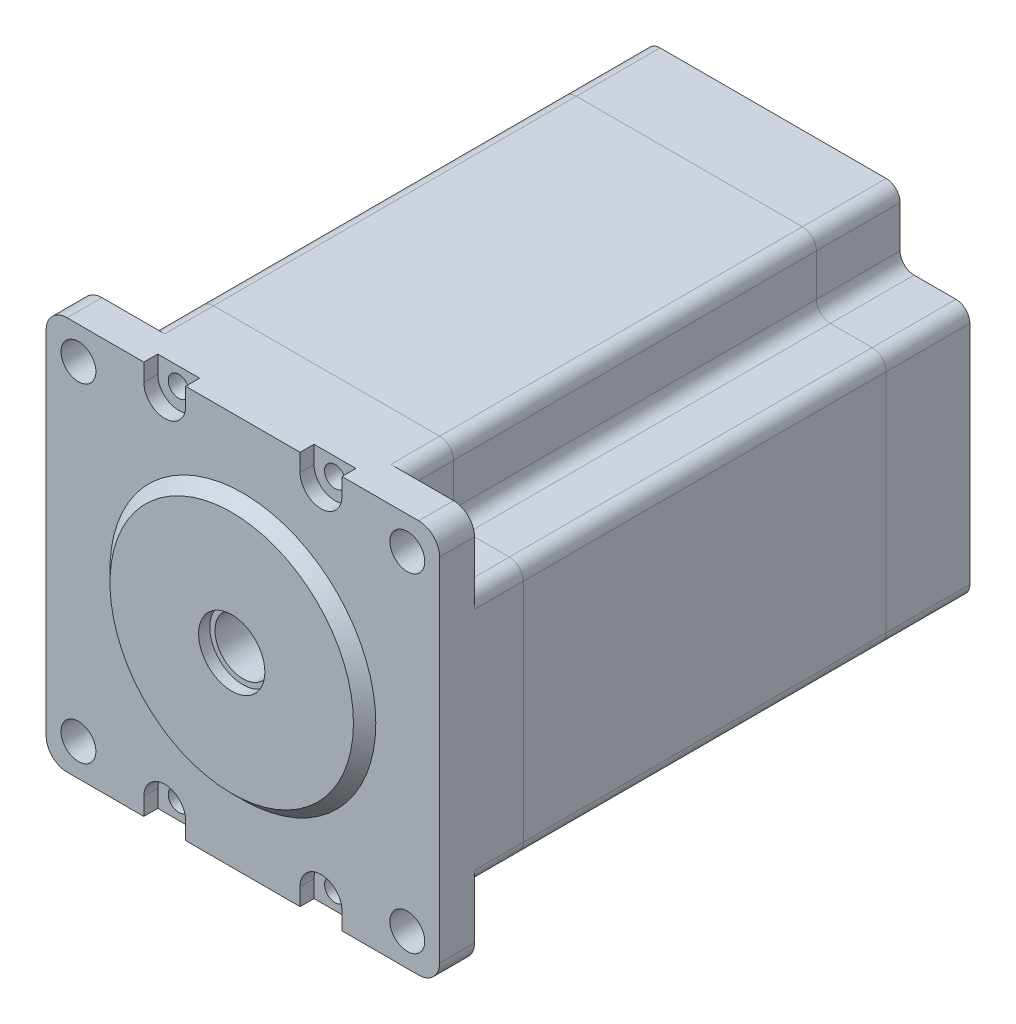
SolidWorks part; units mm, degrees
ref_plane "Ön Düzlem" through (0, 0, 0) normal (0, 0, 1) x (1, 0, 0)
ref_plane "Üst Düzlem" through (0, 0, 0) normal (0, 1, 0) x (1, 0, 0)
ref_plane "Sağ Düzlem" through (0, 0, 0) normal (1, 0, 0) x (0, 0, -1)
sketch "Çizim2" plane through (0, 0, 0) normal (0, 0, 1) x (1, 0, 0)
  line L0 (-28.2, 0) -> (28.2, 0) construction
  line L1 (-25.2, 28.2) -> (25.2, 28.2)
  line L2 (-28.2, 25.2) -> (-28.2, -25.2)
  line L3 (-25.2, -28.2) -> (25.2, -28.2)
  line L4 (28.2, 25.2) -> (28.2, -25.2)
  line L5 (-28.2, 28.2) -> (28.2, -28.2) construction
  line L6 (-28.2, -28.2) -> (28.2, 28.2) construction
  arc A0 (-28.2, -25.2) -> (-25.2, -28.2) centre (-25.2, -25.2) ccw
  arc A1 (25.2, -28.2) -> (28.2, -25.2) centre (25.2, -25.2) ccw
  arc A2 (25.2, 28.2) -> (28.2, 25.2) centre (25.2, 25.2) cw
  arc A3 (-25.2, 28.2) -> (-28.2, 25.2) centre (-25.2, 25.2) ccw
  circle A4 centre (-23.57, 23.57) radius 2.5
  circle A5 centre (23.57, 23.57) radius 2.5
  circle A6 centre (23.57, -23.57) radius 2.5
  circle A7 centre (-23.57, -23.57) radius 2.5
  point P0 (0, 0)
  dimension "D3" = 3
  dimension "D5" = 5
  dimension "D6" = 5
  dimension "D1" = 56.4
  dimension "D2" = 56.4
  dimension "D4" = 47.14
extrude "Yükseklik-Ekstrüzyon1" add sketch "Çizim2" along normal blind 5
sketch "Çizim4" plane through (0, 0, 0) normal (0, 0, -1) x (-1, 0, 0)
  line L0 (-18.2, 26.2) -> (-18.2, 20.2)
  line L1 (-25.2, 28.2) -> (25.2, 28.2) construction
  line L2 (-20.2, 18.2) -> (-26.2, 18.2)
  line L3 (-28.2, -25.2) -> (-28.2, 25.2) construction
  line L4 (26.2, 18.2) -> (20.2, 18.2)
  line L5 (18.2, 20.2) -> (18.2, 26.2)
  line L6 (18.2, -26.2) -> (18.2, -20.2)
  line L7 (20.2, -18.2) -> (26.2, -18.2)
  line L8 (-26.2, -18.2) -> (-20.2, -18.2)
  line L9 (-18.2, -20.2) -> (-18.2, -26.2)
  line L10 (-16.2, 28.2) -> (16.2, 28.2)
  line L11 (28.2, 16.2) -> (28.2, -16.2)
  line L12 (16.2, -28.2) -> (-16.2, -28.2)
  line L13 (-28.2, -16.2) -> (-28.2, 16.2)
  arc A0 (-26.2, -18.2) -> (-28.2, -16.2) centre (-26.2, -16.2) cw
  arc A1 (-20.2, -18.2) -> (-18.2, -20.2) centre (-20.2, -20.2) cw
  arc A2 (-18.2, -26.2) -> (-16.2, -28.2) centre (-16.2, -26.2) ccw
  arc A3 (18.2, -26.2) -> (16.2, -28.2) centre (16.2, -26.2) cw
  arc A4 (18.2, -20.2) -> (20.2, -18.2) centre (20.2, -20.2) cw
  arc A5 (26.2, -18.2) -> (28.2, -16.2) centre (26.2, -16.2) ccw
  arc A6 (26.2, 18.2) -> (28.2, 16.2) centre (26.2, 16.2) cw
  arc A7 (20.2, 18.2) -> (18.2, 20.2) centre (20.2, 20.2) cw
  arc A8 (18.2, 26.2) -> (16.2, 28.2) centre (16.2, 26.2) ccw
  arc A9 (-26.2, 18.2) -> (-28.2, 16.2) centre (-26.2, 16.2) ccw
  arc A10 (-18.2, 26.2) -> (-16.2, 28.2) centre (-16.2, 26.2) cw
  arc A11 (-18.2, 20.2) -> (-20.2, 18.2) centre (-20.2, 20.2) cw
  point P19 (0, 0)
  point P37 (-28.2, 18.2)
  point P40 (-18.2, 28.2)
  dimension "D4" = 2
  dimension "D1" = 10
  dimension "D2" = 10
  dimension "D3" = 4
extrude "Yükseklik-Ekstrüzyon2" add sketch "Çizim4" along normal blind 7
sketch "Çizim5" plane through (0, 0, 5) normal (0, 0, 1) x (1, 0, 0)
  line L0 (-14.2, 28.2) -> (-14.2, 25.7)
  line L1 (25.2, 28.2) -> (-25.2, 28.2) construction
  line L2 (-8.2, 28.2) -> (-8.2, 25.7)
  line L3 (-28.2, 25.2) -> (-28.2, -25.2) construction
  line L4 (-14.2, 28.2) -> (-8.2, 28.2)
  line L5 (-28.2, 0) -> (28.2, 0) construction
  line L6 (28.2, -25.2) -> (28.2, 25.2) construction
  line L7 (0, 28.2) -> (0, -28.2) construction
  line L8 (-25.2, -28.2) -> (25.2, -28.2) construction
  line L9 (-14.2, -28.2) -> (-8.2, -28.2)
  line L10 (-8.2, -28.2) -> (-8.2, -25.7)
  line L11 (-14.2, -28.2) -> (-14.2, -25.7)
  line L12 (14.2, -28.2) -> (14.2, -25.7)
  line L13 (8.2, -28.2) -> (8.2, -25.7)
  line L14 (14.2, -28.2) -> (8.2, -28.2)
  line L15 (14.2, 28.2) -> (8.2, 28.2)
  line L16 (8.2, 28.2) -> (8.2, 25.7)
  line L17 (14.2, 28.2) -> (14.2, 25.7)
  arc A0 (-14.2, 25.7) -> (-8.2, 25.7) centre (-11.2, 25.7) ccw
  arc A1 (-14.2, -25.7) -> (-8.2, -25.7) centre (-11.2, -25.7) cw
  arc A2 (14.2, -25.7) -> (8.2, -25.7) centre (11.2, -25.7) ccw
  arc A3 (14.2, 25.7) -> (8.2, 25.7) centre (11.2, 25.7) cw
  dimension "D1" = 14
  dimension "D2" = 6
  dimension "D3" = 2.5
  dimension "D4" = 2.5
extrude "Kes-Ekstrüzyon1" cut sketch "Çizim5" against normal blind 2
sketch "Çizim6" plane through (0, 0, 5) normal (0, 0, 1) x (1, 0, 0)
  circle A0 centre (0, 0) radius 19.05
  dimension "D1" = 38.1
extrude "Yükseklik-Ekstrüzyon3" add sketch "Çizim6" along normal blind 1.6 separate body
chamfer "Pah1" distance 1.6 angle 45 1 edges at (19.05, 0, 6.6)
sketch "Çizim7" plane through (0, 0, 6.6) normal (0, 0, 1) x (1, 0, 0)
  circle A0 centre (0, 0) radius 4
  dimension "D1" = 8
sketch "Çizim8" plane through (0, 0, -7) normal (0, 0, -1) x (-1, 0, 0)
  line L12 (-26.2, -18.2) -> (-20.2, -18.2)
  line L13 (-18.2, -20.2) -> (-18.2, -26.2)
  line L14 (-16.2, -28.2) -> (16.2, -28.2)
  line L15 (18.2, -26.2) -> (18.2, -20.2)
  line L16 (20.2, -18.2) -> (26.2, -18.2)
  line L17 (28.2, -16.2) -> (28.2, 16.2)
  line L18 (26.2, 18.2) -> (20.2, 18.2)
  line L19 (18.2, 20.2) -> (18.2, 26.2)
  line L20 (16.2, 28.2) -> (-16.2, 28.2)
  line L21 (-18.2, 26.2) -> (-18.2, 20.2)
  line L22 (-20.2, 18.2) -> (-26.2, 18.2)
  line L23 (-28.2, 16.2) -> (-28.2, -16.2)
  line L24 (-26.2, -18.2) -> (-20.2, -18.2)
  line L25 (-18.2, -20.2) -> (-18.2, -26.2)
  line L26 (-16.2, -28.2) -> (16.2, -28.2)
  line L27 (18.2, -26.2) -> (18.2, -20.2)
  line L28 (20.2, -18.2) -> (26.2, -18.2)
  line L29 (28.2, -16.2) -> (28.2, 16.2)
  line L30 (26.2, 18.2) -> (20.2, 18.2)
  line L31 (18.2, 20.2) -> (18.2, 26.2)
  line L32 (16.2, 28.2) -> (-16.2, 28.2)
  line L33 (-18.2, 26.2) -> (-18.2, 20.2)
  line L34 (-20.2, 18.2) -> (-26.2, 18.2)
  line L35 (-28.2, 16.2) -> (-28.2, -16.2)
  arc A12 (-28.2, -16.2) -> (-26.2, -18.2) centre (-26.2, -16.2) ccw
  arc A13 (-18.2, -20.2) -> (-20.2, -18.2) centre (-20.2, -20.2) ccw
  arc A14 (-18.2, -26.2) -> (-16.2, -28.2) centre (-16.2, -26.2) ccw
  arc A15 (16.2, -28.2) -> (18.2, -26.2) centre (16.2, -26.2) ccw
  arc A16 (20.2, -18.2) -> (18.2, -20.2) centre (20.2, -20.2) ccw
  arc A17 (26.2, -18.2) -> (28.2, -16.2) centre (26.2, -16.2) ccw
  arc A18 (28.2, 16.2) -> (26.2, 18.2) centre (26.2, 16.2) ccw
  arc A19 (18.2, 20.2) -> (20.2, 18.2) centre (20.2, 20.2) ccw
  arc A20 (18.2, 26.2) -> (16.2, 28.2) centre (16.2, 26.2) ccw
  arc A21 (-16.2, 28.2) -> (-18.2, 26.2) centre (-16.2, 26.2) ccw
  arc A22 (-20.2, 18.2) -> (-18.2, 20.2) centre (-20.2, 20.2) ccw
  arc A23 (-26.2, 18.2) -> (-28.2, 16.2) centre (-26.2, 16.2) ccw
  arc A24 (-28.2, -16.2) -> (-26.2, -18.2) centre (-26.2, -16.2) ccw
  arc A25 (-18.2, -20.2) -> (-20.2, -18.2) centre (-20.2, -20.2) ccw
  arc A26 (-18.2, -26.2) -> (-16.2, -28.2) centre (-16.2, -26.2) ccw
  arc A27 (16.2, -28.2) -> (18.2, -26.2) centre (16.2, -26.2) ccw
  arc A28 (20.2, -18.2) -> (18.2, -20.2) centre (20.2, -20.2) ccw
  arc A29 (26.2, -18.2) -> (28.2, -16.2) centre (26.2, -16.2) ccw
  arc A30 (28.2, 16.2) -> (26.2, 18.2) centre (26.2, 16.2) ccw
  arc A31 (18.2, 20.2) -> (20.2, 18.2) centre (20.2, 20.2) ccw
  arc A32 (18.2, 26.2) -> (16.2, 28.2) centre (16.2, 26.2) ccw
  arc A33 (-16.2, 28.2) -> (-18.2, 26.2) centre (-16.2, 26.2) ccw
  arc A34 (-20.2, 18.2) -> (-18.2, 20.2) centre (-20.2, 20.2) ccw
  arc A35 (-26.2, 18.2) -> (-28.2, 16.2) centre (-26.2, 16.2) ccw
  dimension "D1" = 0
extrude "Yükseklik-Ekstrüzyon5" add sketch "Çizim8" along normal blind 52 separate body
sketch "Çizim9" plane through (0, 0, -59) normal (0, 0, -1) x (-1, 0, 0)
  line L12 (-26.2, -18.2) -> (-20.2, -18.2)
  line L13 (-18.2, -20.2) -> (-18.2, -26.2)
  line L14 (-16.2, -28.2) -> (16.2, -28.2)
  line L15 (18.2, -26.2) -> (18.2, -20.2)
  line L16 (20.2, -18.2) -> (26.2, -18.2)
  line L17 (28.2, -16.2) -> (28.2, 16.2)
  line L18 (26.2, 18.2) -> (20.2, 18.2)
  line L19 (18.2, 20.2) -> (18.2, 26.2)
  line L20 (16.2, 28.2) -> (-16.2, 28.2)
  line L21 (-18.2, 26.2) -> (-18.2, 20.2)
  line L22 (-20.2, 18.2) -> (-26.2, 18.2)
  line L23 (-28.2, 16.2) -> (-28.2, -16.2)
  line L24 (-26.2, -18.2) -> (-20.2, -18.2)
  line L25 (-18.2, -20.2) -> (-18.2, -26.2)
  line L26 (-16.2, -28.2) -> (16.2, -28.2)
  line L27 (18.2, -26.2) -> (18.2, -20.2)
  line L28 (20.2, -18.2) -> (26.2, -18.2)
  line L29 (28.2, -16.2) -> (28.2, 16.2)
  line L30 (26.2, 18.2) -> (20.2, 18.2)
  line L31 (18.2, 20.2) -> (18.2, 26.2)
  line L32 (16.2, 28.2) -> (-16.2, 28.2)
  line L33 (-18.2, 26.2) -> (-18.2, 20.2)
  line L34 (-20.2, 18.2) -> (-26.2, 18.2)
  line L35 (-28.2, 16.2) -> (-28.2, -16.2)
  arc A12 (-28.2, -16.2) -> (-26.2, -18.2) centre (-26.2, -16.2) ccw
  arc A13 (-18.2, -20.2) -> (-20.2, -18.2) centre (-20.2, -20.2) ccw
  arc A14 (-18.2, -26.2) -> (-16.2, -28.2) centre (-16.2, -26.2) ccw
  arc A15 (16.2, -28.2) -> (18.2, -26.2) centre (16.2, -26.2) ccw
  arc A16 (20.2, -18.2) -> (18.2, -20.2) centre (20.2, -20.2) ccw
  arc A17 (26.2, -18.2) -> (28.2, -16.2) centre (26.2, -16.2) ccw
  arc A18 (28.2, 16.2) -> (26.2, 18.2) centre (26.2, 16.2) ccw
  arc A19 (18.2, 20.2) -> (20.2, 18.2) centre (20.2, 20.2) ccw
  arc A20 (18.2, 26.2) -> (16.2, 28.2) centre (16.2, 26.2) ccw
  arc A21 (-16.2, 28.2) -> (-18.2, 26.2) centre (-16.2, 26.2) ccw
  arc A22 (-20.2, 18.2) -> (-18.2, 20.2) centre (-20.2, 20.2) ccw
  arc A23 (-26.2, 18.2) -> (-28.2, 16.2) centre (-26.2, 16.2) ccw
  arc A24 (-28.2, -16.2) -> (-26.2, -18.2) centre (-26.2, -16.2) ccw
  arc A25 (-18.2, -20.2) -> (-20.2, -18.2) centre (-20.2, -20.2) ccw
  arc A26 (-18.2, -26.2) -> (-16.2, -28.2) centre (-16.2, -26.2) ccw
  arc A27 (16.2, -28.2) -> (18.2, -26.2) centre (16.2, -26.2) ccw
  arc A28 (20.2, -18.2) -> (18.2, -20.2) centre (20.2, -20.2) ccw
  arc A29 (26.2, -18.2) -> (28.2, -16.2) centre (26.2, -16.2) ccw
  arc A30 (28.2, 16.2) -> (26.2, 18.2) centre (26.2, 16.2) ccw
  arc A31 (18.2, 20.2) -> (20.2, 18.2) centre (20.2, 20.2) ccw
  arc A32 (18.2, 26.2) -> (16.2, 28.2) centre (16.2, 26.2) ccw
  arc A33 (-16.2, 28.2) -> (-18.2, 26.2) centre (-16.2, 26.2) ccw
  arc A34 (-20.2, 18.2) -> (-18.2, 20.2) centre (-20.2, 20.2) ccw
  arc A35 (-26.2, 18.2) -> (-28.2, 16.2) centre (-26.2, 16.2) ccw
  dimension "D1" = 0
extrude "Yükseklik-Ekstrüzyon6" add sketch "Çizim9" along normal blind 12 separate body
sketch "Çizim10" plane through (0, 0, 3) normal (0, 0, 1) x (1, 0, 0)
  line L0 (0, 28.2) -> (0, -28.2) construction
  line L1 (8.2, 28.2) -> (-8.2, 28.2) construction
  line L2 (-8.2, -28.2) -> (8.2, -28.2) construction
  line L3 (-28.2, 0) -> (28.2, 0) construction
  line L4 (-28.2, 25.2) -> (-28.2, -25.2) construction
  line L5 (28.2, -25.2) -> (28.2, 25.2) construction
  circle A0 centre (-11.2, 25.7) radius 1.5
  circle A1 centre (-11.2, -25.7) radius 1.5
  circle A2 centre (11.2, -25.7) radius 1.5
  circle A3 centre (11.2, 25.7) radius 1.5
  dimension "D1" = 3
extrude "Kes-Ekstrüzyon3" cut sketch "Çizim10" against normal blind 10
extrude "Kes-Ekstrüzyon4" cut sketch "Çizim7" against normal up to surface (77.6 mm away) up to face at (0, 0, -71)
sketch "Çizim11" plane through (0, 0, 6.6) normal (0, 0, 1) x (1, 0, 0)
  circle A0 centre (0, 0) radius 4.75
  dimension "D1" = 9.5
extrude "Kes-Ekstrüzyon5" cut sketch "Çizim11" against normal blind 1.6
